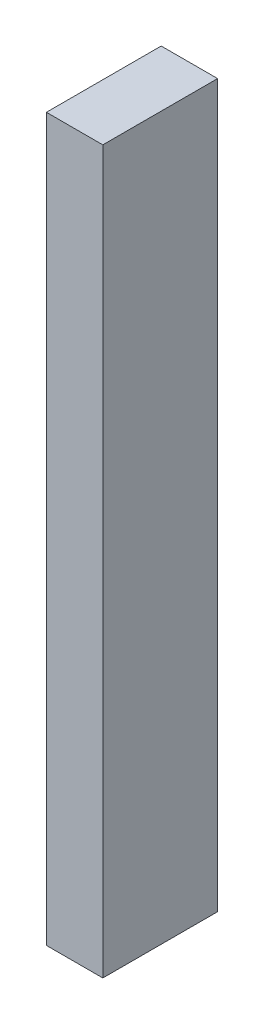
SolidWorks part; units mm, degrees
ref_plane "Front Plane" through (0, 0, 0) normal (0, 0, 1) x (1, 0, 0)
ref_plane "Top Plane" through (0, 0, 0) normal (0, 1, 0) x (1, 0, 0)
ref_plane "Right Plane" through (0, 0, 0) normal (1, 0, 0) x (0, 0, -1)
sketch "Sketch1" plane through (0, 0, 0) normal (0, 1, 0) x (1, 0, 0)
  line L1 (0, 0) -> (25.4, 0)
  line L2 (0, 0) -> (0, 50.8)
  line L3 (0, 50.8) -> (25.4, 50.8)
  line L4 (25.4, 0) -> (25.4, 50.8)
  dimension "D1" = 25.4
  dimension "D2" = 50.8
extrude "Boss-Extrude1" add sketch "Sketch1" along normal blind 558.8
sketch "Sketch2" plane through (0, 0, -50.8) normal (0, 0, -1) x (-1, 0, 0)
  line L0 (-25.4, 558.8) -> (0, 558.8) construction
  line L1 (-25.4, 558.8) -> (-25.4, 0) construction
  circle A0 centre (-12.7, 546.1) radius 6.35
  dimension "D1" = 12.7
  dimension "D2" = 12.7
extrude "Boss-Extrude2" add sketch "Sketch2" along normal blind 6.35
sketch "Sketch3" plane through (0, 0, 0) normal (-1, 0, 0) x (0, 0, 1)
  line L1 (0, 0) -> (-50.8, 0)
  line L2 (0, 0) -> (0, 558.8)
  line L3 (0, 558.8) -> (-50.8, 558.8)
  line L4 (-50.8, 0) -> (-50.8, 558.8)
extrude "Boss-Extrude3" add sketch "Sketch3" along normal blind 18.288
sketch "Sketch4" plane through (0, 0, -50.8) normal (0, 0, -1) x (-1, 0, 0)
  line L1 (-25.4, 558.8) -> (18.288, 558.8)
  line L2 (-25.4, 558.8) -> (-25.4, 0)
  line L3 (-25.4, 0) -> (18.288, 0)
  line L4 (18.288, 558.8) -> (18.288, 0)
  line L5 (-25.4, 558.8) -> (18.288, 558.8) construction
  line L6 (-25.4, 558.8) -> (-25.4, 0) construction
  line L7 (18.288, 558.8) -> (18.288, 0) construction
  line L8 (-25.4, 0) -> (18.288, 0) construction
extrude "Boss-Extrude4" add sketch "Sketch4" along normal blind 19.05
sketch "Sketch5" plane through (0, 0, 0) normal (0, 0, 1) x (1, 0, 0)
  line L0 (-18.288, 558.8) -> (25.4, 558.8) construction
  line L1 (-18.288, 558.8) -> (25.4, 558.8)
  line L2 (-18.288, 558.8) -> (-18.288, 0)
  line L3 (-18.288, 0) -> (25.4, 0)
  line L4 (25.4, 558.8) -> (25.4, 0)
  line L5 (-18.288, 0) -> (-18.288, 558.8) construction
  line L6 (25.4, 558.8) -> (25.4, 0) construction
  line L7 (-18.288, 0) -> (25.4, 0) construction
extrude "Boss-Extrude5" add sketch "Sketch5" along normal blind 19.05
